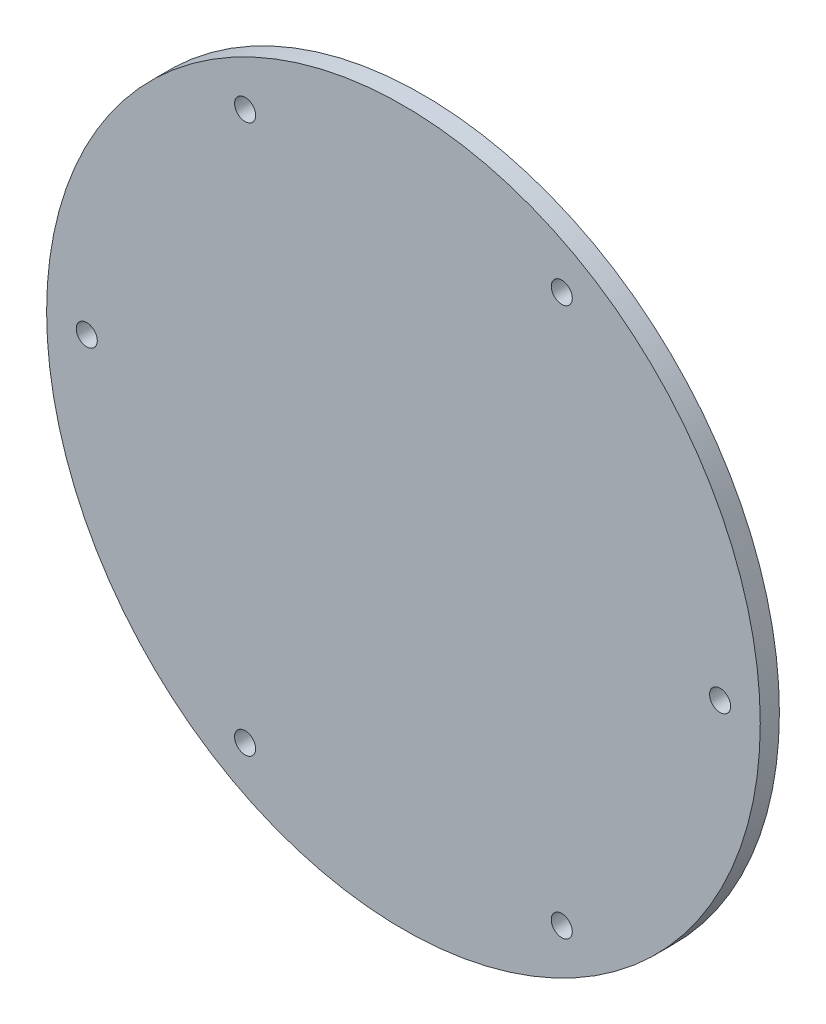
SolidWorks part; units mm, degrees
ref_plane "Front Plane" through (0, 0, 0) normal (0, 0, 1) x (1, 0, 0)
ref_plane "Top Plane" through (0, 0, 0) normal (0, 1, 0) x (1, 0, 0)
ref_plane "Right Plane" through (0, 0, 0) normal (1, 0, 0) x (0, 0, -1)
sketch "Sketch1" plane through (0, 0, 0) normal (0, 0, 1) x (1, 0, 0)
  circle A1 centre (-24.8353, -43.0159) radius 2.3 construction
  circle A2 centre (24.8353, -43.0159) radius 2.3 construction
  circle A3 centre (49.6705, 0) radius 2.3 construction
  circle A4 centre (24.8353, 43.0159) radius 2.3 construction
  circle A5 centre (-24.8352, 43.0159) radius 2.3 construction
  circle A6 centre (-49.6705, 0) radius 2.3 construction
  circle A7 centre (0, 0) radius 55.9705 construction
  circle A9 centre (-24.8353, -43.0159) radius 2.3 construction
  circle A10 centre (24.8353, -43.0159) radius 2.3 construction
  circle A11 centre (49.6705, 0) radius 2.3 construction
  circle A12 centre (24.8353, 43.0159) radius 2.3 construction
  circle A13 centre (-24.8352, 43.0159) radius 2.3 construction
  circle A14 centre (-49.6705, 0) radius 2.3 construction
  circle A15 centre (0, 0) radius 55.9705
  circle A16 centre (49.6705, 0) radius 1.65
  circle A17 centre (24.8353, 43.0159) radius 1.65
  circle A18 centre (-24.8352, 43.0159) radius 1.65
  circle A19 centre (-49.6705, 0) radius 1.65
  circle A20 centre (-24.8353, -43.0159) radius 1.65
  circle A21 centre (24.8353, -43.0159) radius 1.65
  point P25 (-24.8352, 43.0159)
  point P26 (24.8353, 43.0159)
  point P27 (49.6705, 0)
  point P28 (24.8353, -43.0159)
  point P29 (-24.8353, -43.0159)
  point P30 (-49.6705, 0)
  dimension "D1" = 3.3
extrude "Boss-Extrude1" add sketch "Sketch1" along normal blind 3
sketch "Sketch3" plane through (0, 0, 0) normal (0, 0, -1) x (-1, 0, 0)
  circle A0 centre (0, 0) radius 37.85
  dimension "D1" = 75.7
extrude "Boss-Extrude2" add sketch "Sketch3" along normal blind 2 draft 2
chamfer "Chamfer1" distance 0.5 angle 45 1 edges at (-37.7802, 0, -2) first distance on face at (-37.7802, 0, -2)
equation "\"D1@Sketch3\"=3in-.5mm"
